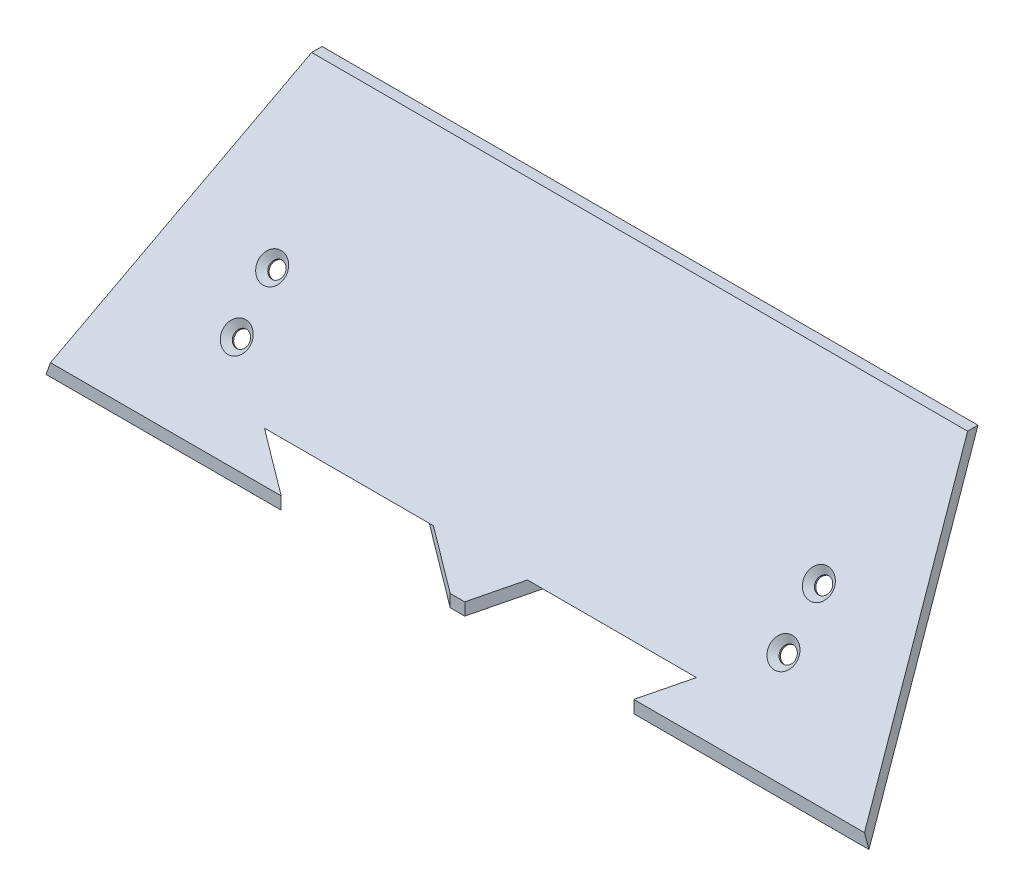
SolidWorks part; units mm, degrees
material "Delrin 2700 NC010, Low Viscosity Acetal Copolymer (SS)"
ref_plane "Front Plane" through (0, 0, 0) normal (0, 0, 1) x (1, 0, 0)
ref_plane "Top Plane" through (0, 0, 0) normal (0, 1, 0) x (1, 0, 0)
ref_plane "Right Plane" through (0, 0, 0) normal (1, 0, 0) x (0, 0, -1)
sketch "Sketch2" plane through (0, 0, 0) normal (1, 0, 0) x (0, 0, -1)
  line L0 (0, 0) -> (-2.3622, 0)
  line L1 (-2.3622, 0) -> (45.4805, 57.0167)
  line L2 (45.4805, 57.0167) -> (47.8427, 57.0167)
  line L3 (47.8427, 57.0167) -> (0, 0)
  dimension "D1" = 50
  dimension "D2" = 74.43
  dimension "D3" = 2.3622
extrude "Boss-Extrude1" add sketch "Sketch2" along normal blind 186.9479
sketch "Sketch3" plane through (0, 0, 0) normal (-1, 0, 0) x (0, 0, 1)
  line L0 (-4.1057, 4.893) -> (-4.1057, 7.7082)
  line L1 (-45.4805, 57.0167) -> (2.3622, 0) construction
  line L2 (-4.1057, 7.7082) -> (2.3622, 0)
  line L3 (2.3622, 0) -> (0, 0)
  line L4 (0, 0) -> (-4.1057, 4.893)
  line L5 (0, 0) -> (-47.8427, 57.0167) construction
  line L6 (-4.1057, 4.893) -> (-4.1057, -12.9833) construction
extrude "Cut-Extrude1" cut sketch "Sketch3" against normal through all
sketch "Sketch4" plane through (93.4965, -1.9814, -4.1057) normal (0, 0, -1) x (-1, 0, 0)
  line L0 (93.4965, 58.998) -> (74.525, 58.998)
  line L1 (-93.4515, 58.998) -> (93.4965, 58.998) construction
  line L3 (74.525, 58.998) -> (93.4965, 6.8743)
  line L4 (93.4965, 6.8743) -> (93.4965, 58.998)
  line L5 (-93.4515, 6.8743) -> (-93.4515, 58.998)
  line L6 (-93.4515, 58.998) -> (-74.48, 58.998)
  line L7 (-74.48, 58.998) -> (-93.4515, 6.8743)
  dimension "D1" = 20
  dimension "D2" = 20
extrude "Cut-Extrude2" cut sketch "Sketch4" along normal through all
hole_wizard "CSK for M3 Flat Head Machine Screw1" positions "Sketch5" profile "Sketch6" countersink size "M3" standard "ANSI Metric"
sketch "Sketch5" plane through (0, 1.1632, 1.3862) normal (0, 0.6428, 0.766) x (1, 0, 0)
  point P0 (31.3777, 39.6549)
  point P2 (31.3777, 27.1455)
sketch "Sketch6" plane through (31.3777, 31.5406, -24.1035) normal (1, 0, 0) x (0, -0.766, 0.6428)
  line L0 (0, 0) -> (0, 5)
  line L1 (0, 5) -> (1.75, 5)
  line L2 (1.75, 5) -> (1.75, 1.4)
  line L3 (1.75, 1.4) -> (3.15, 0)
  line L5 (3.15, 0) -> (0, 0)
  line L6 (-1.75, 1.4) -> (-3.15, 0) construction
  line L10 (0, 5) -> (-1.75, 5) construction
  line L11 (0, -6.35) -> (0, 107.95) construction
  dimension "Hole Dia." = 3.5
  dimension "Hole Depth" = 5
  dimension "Near C'Sink Dia." = 6.3
  dimension "Near C'Sink Angle" = 90
  dimension "Drill Angle" = 180
ref_plane "Plane1" through (93.474, 0, 0) normal (1, 0, 0) x (0, 0, -1)
mirror "Mirror1" about plane through (93.474, 0, 0) normal (1, 0, 0) of "CSK for M3 Flat Head Machine Screw1"
ref_plane "Plane2" through (112.633, 0, -65.0287) normal (-0.866, 0, 0.5) x (0.5, 0, 0.866)
sketch "Sketch7" plane through (112.633, 0, -65.0287) normal (-0.866, 0, 0.5) x (0.5, 0, 0.866)
  line L0 (46.0064, 4.9186) -> (46.0064, 3.9186)
  line L1 (61.2064, 11.9186) -> (46.0064, 11.9186)
  line L2 (61.2064, 11.9186) -> (61.2064, 4.9186)
  line L3 (61.2064, 4.9186) -> (46.0064, 4.9186)
  line L4 (46.0064, 11.9186) -> (46.0064, 4.9186)
  line L5 (46.0064, 3.9186) -> (61.2064, 3.9186)
  line L6 (61.2064, 3.9186) -> (61.2064, 4.9186)
  line L7 (63.2064, 13.9186) -> (63.2064, 4.9186)
  line L8 (63.2064, 13.9186) -> (44.0064, 13.9186)
  line L9 (44.0064, 13.9186) -> (44.0064, 4.9186)
  line L10 (44.0064, 4.9186) -> (44.0064, 2.9186)
  line L11 (44.0064, 2.9186) -> (63.2064, 2.9186)
  line L12 (63.2064, 2.9186) -> (63.2064, 4.9186)
  dimension "D1" = 1
  dimension "D3" = 2
  dimension "D2" = 2
extrude "Cut-Extrude3" cut sketch "Sketch7" along normal up to surface (35.2023 mm away) contours L1 L4 L3 L2 | L5 L6 L3 L0 | L11 L12 L7 L8 L9 L10 L6 L5 L0 L4 L1 L2 region at (139.4362, 4.4186, -18.6042) region at (139.4362, 8.4186, -18.6042) region at (144.1256, 9.4186, -10.482) up to face at (155.5703, 29.1276, -22.0787)
mirror "Mirror2" about plane through (93.474, 0, 0) normal (1, 0, 0) of "Cut-Extrude3"
